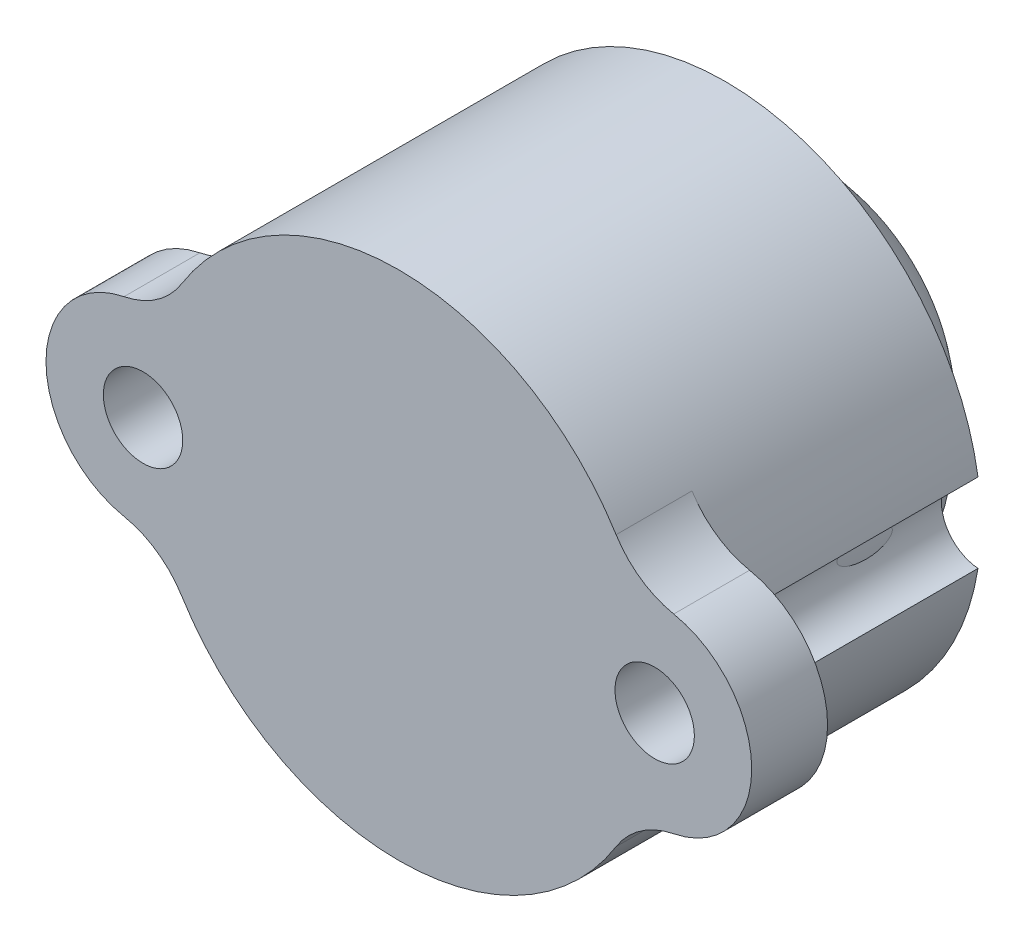
SolidWorks part; units mm, degrees
material "Nickel"
ref_plane "Plan de face" through (0, 0, 0) normal (0, 0, 1) x (1, 0, 0)
ref_plane "Plan de dessus" through (0, 0, 0) normal (0, 1, 0) x (1, 0, 0)
ref_plane "Plan de droite" through (0, 0, 0) normal (1, 0, 0) x (0, 0, -1)
sketch "Esquisse1" plane through (0, 0, 0) normal (0, 0, 1) x (1, 0, 0)
  circle A0 centre (0, 0) radius 7.366
  dimension "D1" = 14.732
extrude "Boss.-Extru.1" add sketch "Esquisse1" along normal blind 9.398
sketch "Esquisse2" plane through (0, 0, 9.398) normal (0, 0, 1) x (1, 0, 0)
  line L0 (-7.366, 0) -> (7.366, 0) construction
  line L1 (-7.366, 2.794) -> (7.366, 2.794)
  line L2 (-7.366, -2.794) -> (7.366, -2.794)
  line L3 (-10.16, 0) -> (10.16, 0)
  arc A0 (-7.366, 2.794) -> (-7.366, -2.794) centre (-7.366, 0) ccw
  arc A1 (7.366, -2.794) -> (7.366, 2.794) centre (7.366, 0) ccw
  point P2 (0, 0)
  point P7 (0, 0)
  circle M3 centre (0, 0) radius 7.366
  dimension "D2" = 20.32
  dimension "D1" = 14.732
extrude "Boss.-Extru.2" add sketch "Esquisse2" against normal blind 2.1844 contours L3 A1 L1 M3 | L2 A1 L3 M3 | L3 A0 L2 M3 | L1 A0 L3 M3 region at (-8.4491, 1.2554, 9.398) region at (-8.4491, -1.2554, 9.398) region at (8.4491, 1.2554, 9.398) region at (8.4491, -1.2554, 9.398)
fillet "Congé1" radius 2.54 4 edges at (6.8155, 2.794, 8.3058) (6.8155, -2.794, 8.3058) (-6.8155, -2.794, 8.3058) (-6.8155, 2.794, 8.3058)
sketch "Esquisse3" plane through (0, 0, 9.398) normal (0, 0, 1) x (1, 0, 0)
  line L0 (-7.366, 0) -> (7.366, 0)
  circle A0 centre (-7.366, 0) radius 1.143
  circle A1 centre (7.366, 0) radius 1.143
  point P4 (0, 0)
  dimension "D2" = 2.286
  dimension "D3" = 2.286
  dimension "D1" = 14.732
extrude "Enlèv. mat.-Extru.2" cut sketch "Esquisse3" against normal through all contours A0 | A1 region at (-8.4767, 0, 9.398)
sketch "Esquisse4" plane through (0, 0, 0) normal (1, 0, 0) x (0, 0, -1)
  line L2 (-7.0373, 0) -> (7.1163, 0) construction
  line L3 (-8.4836, 0) -> (4.064, 0)
  line L4 (-9.398, -3.8892) -> (-9.398, -7.366) construction
  arc A0 (4.064, 0) -> (-8.4836, 0) centre (-2.2098, 0) ccw
  dimension "D1" = 12.5476
  dimension "D2" = 13.462
revolve "Révolution4" add sketch "Esquisse4" angle 360 about L2
sketch "Esquisse5" plane through (0, 0, 9.398) normal (0, 0, 1) x (1, 0, 0)
  line L0 (-12.5359, 0) -> (12.4243, 0) construction
  point P3 (-0.0558, 0)
